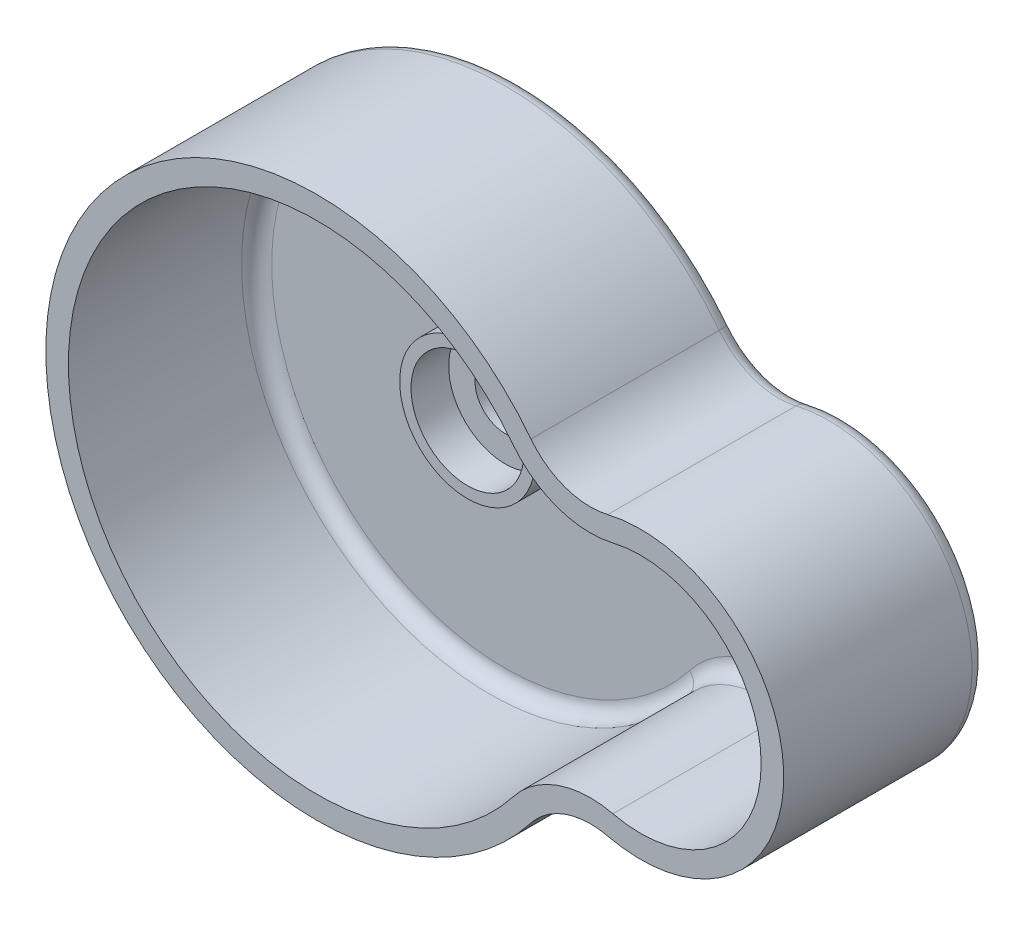
SolidWorks part; units mm, degrees
material "Stainless Steel (ferritic)"
ref_plane "Front Plane" through (0, 0, 0) normal (0, 0, 1) x (1, 0, 0)
ref_plane "Top Plane" through (0, 0, 0) normal (0, 1, 0) x (1, 0, 0)
ref_plane "Right Plane" through (0, 0, 0) normal (1, 0, 0) x (0, 0, -1)
sketch "Sketch1" plane through (0, 0, 0) normal (0, 0, 1) x (1, 0, 0)
  circle A0 centre (0, 0) radius 7.5
  circle A1 centre (0, 0) radius 4
  circle A2 centre (0, 0) radius 9
  circle A3 centre (43, 0) radius 9
  circle A4 centre (43, 0) radius 4
  circle A5 centre (43, 0) radius 7.5
  arc A6 (28.4287, 22.0864) -> (28.4287, -22.0864) centre (0, 0) ccw
  arc A8 (38.6271, -18.4899) -> (38.6271, 18.4899) centre (43, 0) ccw
  arc A9 (35.6279, 5.1626) -> (32.3721, 15.7495) centre (0, 0) ccw construction
  arc A10 (32.3721, -15.7495) -> (35.6279, -5.1626) centre (0, 0) ccw construction
  arc A11 (35.9157, 2.4622) -> (35.6279, 5.1626) centre (0, 0) ccw construction
  arc A12 (35.6279, -5.1626) -> (35.9157, -2.4622) centre (0, 0) ccw construction
  arc A13 (35.9157, -2.4622) -> (35.9157, 2.4622) centre (0, 0) ccw construction
  arc A14 (32.3721, 15.7495) -> (32.3721, -15.7495) centre (43, 0) ccw construction
  arc A15 (28.4287, -22.0864) -> (38.6271, -18.4899) centre (36.3256, -28.2215) cw
  arc A16 (28.4287, 22.0864) -> (38.6271, 18.4899) centre (36.3256, 28.2215) ccw
  arc A17 (26.0597, 20.2458) -> (26.0597, -20.2458) centre (0, 0) ccw
  arc A18 (26.0597, -20.2458) -> (39.3176, -15.5705) centre (36.3256, -28.2215) cw
  arc A19 (39.3176, -15.5705) -> (39.3176, 15.5705) centre (43, 0) ccw
  arc A20 (26.0597, 20.2458) -> (39.3176, 15.5705) centre (36.3256, 28.2215) ccw
  dimension "D1" = 8
  dimension "D2" = 15
  dimension "D3" = 18
  dimension "D5" = 72
  dimension "D6" = 38
  dimension "D7" = 10
  dimension "D4" = 43
  dimension "D8" = 3
extrude "Boss-Extrude1" add sketch "Sketch1" along normal blind 2 contours A16 A6 A15 A8 A17 A20 A19 A18 | A20 A17 A18 A19 A3 A2 | A0 A1 | A2 A0 | A5 A4 | A3 A5 region at (-7.2879, 0, 0) region at (-8.7454, 0, 0) region at (34.2546, 0, 0) region at (35.7121, 0, 0) region at (32.5954, 17.6439, 0) region at (31.6256, 14.8937, 0)
extrude "Boss-Extrude2" add sketch "Sketch1<3>" along normal blind 7 contours A2 A0 | A3 A5 region at (-8.7454, 0, 0) region at (34.2546, 0, 0)
sketch "Sketch1<3>" plane through (0, 0, 0) normal (0, 0, 1) x (1, 0, 0) same geometry as "Sketch1"
extrude "Boss-Extrude3" add sketch "Sketch1<4>" along normal blind 27 contours A16 A6 A15 A8 A17 A20 A19 A18 region at (32.5954, 17.6439, 0)
sketch "Sketch1<4>" plane through (0, 0, 0) normal (0, 0, 1) x (1, 0, 0) same geometry as "Sketch1"
fillet "Fillet1" radius 2 8 edges at (32.9998, -18.7907, 0) (-36, 0, 0) (32.9998, 18.7907, 0) (32.0021, -15.9615, 2) (59, 0, 2) (32.0021, 15.9615, 2) (62, 0, 0) (-33, 0, 2)
